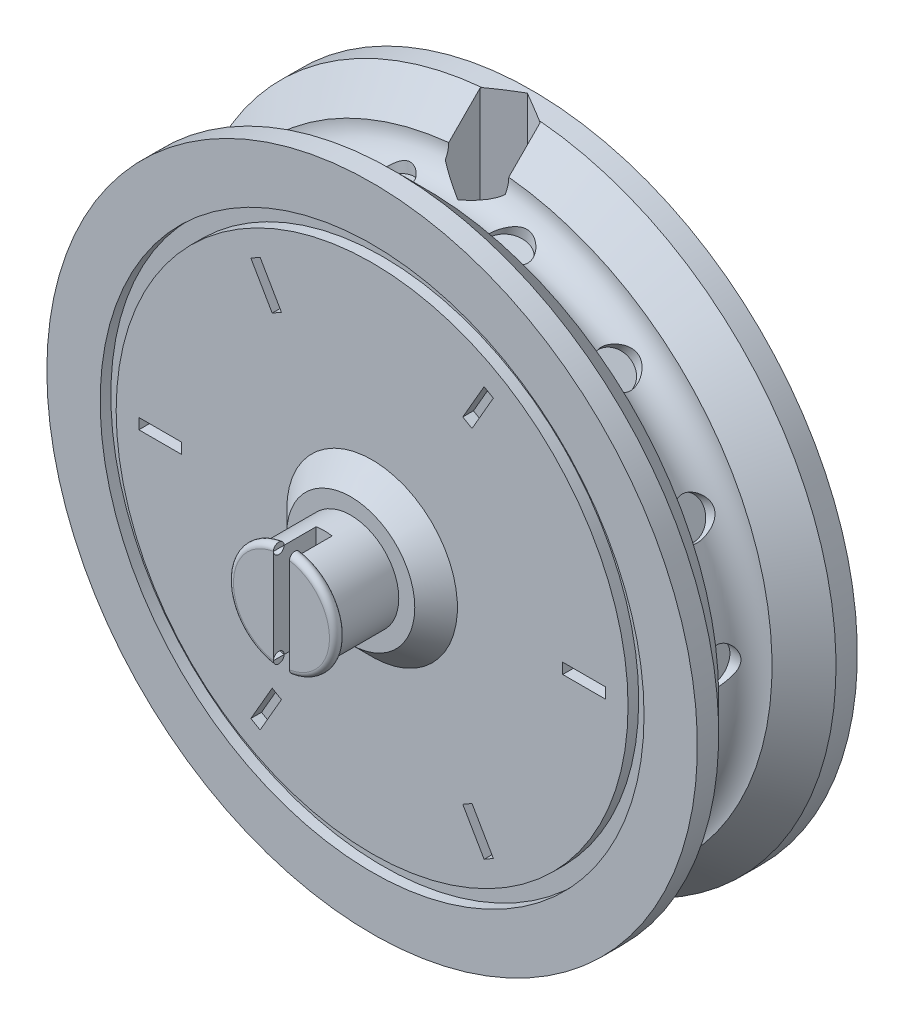
SolidWorks part; units mm, degrees
ref_plane "Alzado" through (0, 0, 0) normal (0, 0, 1) x (1, 0, 0)
ref_plane "Planta" through (0, 0, 0) normal (0, 1, 0) x (1, 0, 0)
ref_plane "Vista lateral" through (0, 0, 0) normal (1, 0, 0) x (0, 0, -1)
ref_plane "Plano1" through (0, 0, -7.7) normal (0, 0, 1) x (1, 0, 0)
sketch "Croquis2" plane through (0, 0, -7.7) normal (0, 0, 1) x (1, 0, 0)
  line L0 (2.829, 4.9) -> (-2.829, 4.9) construction
  line L1 (-3.06, -5.3) -> (3.06, -5.3)
  line L2 (3.06, -5.3) -> (6.1199, 0)
  line L3 (6.1199, 0) -> (3.06, 5.3)
  line L4 (3.06, 5.3) -> (-3.06, 5.3)
  line L5 (-3.06, 5.3) -> (-6.1199, 0)
  line L6 (-6.1199, 0) -> (-3.06, -5.3)
  line L8 (-8.4293, 0) -> (-4.2147, -7.3)
  line L9 (-4.2147, -7.3) -> (4.2147, -7.3)
  line L10 (4.2147, -7.3) -> (8.4293, 0)
  line L11 (8.4293, 0) -> (4.2147, 7.3)
  line L12 (4.2147, 7.3) -> (-4.2147, 7.3)
  line L13 (-4.2147, 7.3) -> (-8.4293, 0)
  circle A0 centre (0, 0) radius 5.3 construction
  circle A1 centre (0, 0) radius 7.3 construction
  dimension "D1" = 0.4
  dimension "D2" = 2
extrude "Saliente-Extruir1" add sketch "Croquis2" along normal up to surface (7.7 mm away)
sketch "Croquis3" plane through (0, -7.3, 0) normal (0, -1, 0) x (1, 0, 0)
  circle A0 centre (0, -4) radius 1.65
  circle A1 centre (0, -4) radius 1.65 construction
extrude "Cortar-Extruir1" cut sketch "Croquis3" against normal through all both and the other way through all
sketch "Croquis4" plane through (0, 0, 0) normal (0, 1, 0) x (1, 0, 0)
  line L0 (0, 7.7) -> (0, -7.3)
  line L1 (-4.2147, 7.7) -> (4.2147, 7.7) construction
  line L2 (0, -7.3) -> (30.5, -7.3)
  line L3 (30.5, -7.3) -> (30.5, -5.3)
  line L4 (30.5, -5.3) -> (27.5, -2.3)
  line L5 (27.5, -2.3) -> (27.5, 2.7) construction
  line L6 (27.5, 2.7) -> (30.5, 5.7)
  line L7 (30.5, 5.7) -> (30.5, 7.7)
  line L8 (30.5, 7.7) -> (0, 7.7)
  line L9 (25, 0.2) -> (0, 0.2) construction
  line L10 (15.25, -7.3) -> (15.25, 0.2) construction
  line L11 (15.25, 0.2) -> (15.25, 7.7) construction
  arc A1 (27.5, 2.7) -> (27.5, -2.3) centre (27.5, 0.2) ccw
  dimension "D1" = 5
  dimension "D2" = 25
  dimension "D3" = 15
  dimension "D4" = 3
  dimension "D5" = 2
revolve "Revolución1" add sketch "Croquis4" angle 360 about L0
sketch "Croquis5" plane through (0, 4.9, 0) normal (0, 1, 0) x (1, 0, 0)
  circle A0 centre (0, 4) radius 2.6
  circle A1 centre (0, 4) radius 1.65 construction
  dimension "D1" = 5.2
  dimension "D2" = 0
extrude "Cortar-Extruir2" cut sketch "Croquis5" against normal through all
sketch "Croquis6" plane through (0, 0, 0) normal (0, 1, 0) x (1, 0, 0)
  line L1 (0, 0.75) -> (2.8146, 2.375)
  line L2 (2.8146, 2.375) -> (2.8146, 5.625)
  line L3 (2.8146, 5.625) -> (0, 7.25)
  line L4 (0, 7.25) -> (-2.8146, 5.625)
  line L5 (-2.8146, 5.625) -> (-2.8146, 2.375)
  line L6 (-2.8146, 2.375) -> (0, 0.75)
  circle A0 centre (0, 4) radius 3.25 construction
  dimension "D1" = 6.5
extrude "Cortar-Extruir3" cut sketch "Croquis6" along normal through all
sketch "Croquis7" plane through (0, 0, 7.3) normal (0, 0, 1) x (1, 0, 0)
  circle A0 centre (0, 0) radius 6
  dimension "D1" = 12
extrude "Saliente-Extruir2" add sketch "Croquis7" along normal blind 2
sketch "Croquis8" plane through (0, 0, 9.3) normal (0, 0, 1) x (1, 0, 0)
  circle A0 centre (0, 0) radius 4.5
  dimension "D1" = 9
extrude "Saliente-Extruir3" add sketch "Croquis8" along normal blind 5.5
chamfer "Chaflán1" distance 2 angle 45 1 edges at (6, 0, 7.3)
sketch "Croquis9" plane through (0, 0, 0) normal (0, 1, 0) x (1, 0, 0)
  line L0 (-4.5, -14.8) -> (-4.5, -15.3) construction
  line L1 (0, -14.8) -> (0, -15.8)
  line L2 (-4.5, -14.8) -> (4.5, -14.8) construction
  line L3 (0, -15.8) -> (-4.5, -15.8)
  line L4 (-4.5, -15.8) -> (-4.5, -14.8)
  line L5 (-4.5, -14.8) -> (0, -14.8)
  circle A0 centre (-4.5, -15.3) radius 0.5
  dimension "D1" = 1
revolve "Revolución2" add sketch "Croquis9" angle 360 about L1 region at (-2.0552, 0, 15.3) region at (-4.7122, 0, 15.3)
sketch "Croquis10" plane through (0, 0, 15.8) normal (0, 0, 1) x (1, 0, 0)
  line L1 (-0.75, 5) -> (0.75, 5)
  line L2 (-0.75, 5) -> (-0.75, -5)
  line L3 (-0.75, -5) -> (0.75, -5)
  line L4 (0.75, 5) -> (0.75, -5)
  line L5 (-0.75, 5) -> (0.75, -5) construction
  line L6 (-0.75, -5) -> (0.75, 5) construction
  circle A0 centre (0, 0) radius 5 construction
  point P0 (0, 0)
  dimension "D1" = 1.5
extrude "Cortar-Extruir6" cut sketch "Croquis10" against normal blind 4
sketch "Croquis12" plane through (0, 0, -7.7) normal (0, 0, -1) x (-1, 0, 0)
  line L1 (6.1199, 0) -> (3.06, 5.3)
  line L2 (3.06, 5.3) -> (-3.06, 5.3)
  line L3 (-3.06, 5.3) -> (-6.1199, 0)
  line L4 (-6.1199, 0) -> (-3.06, -5.3)
  line L5 (-3.06, -5.3) -> (3.06, -5.3)
  line L6 (3.06, -5.3) -> (6.1199, 0)
  circle A0 centre (0, 0) radius 5.3 construction
extrude "Cortar-Extruir7" cut sketch "Croquis12" against normal blind 8
sketch "Croquis13" plane through (0, 0, 0) normal (1, 0, 0) x (0, 0, -1)
  line L0 (0.2, 25) -> (0.2, -25) construction
  line L1 (0.2, 25) -> (-2.3, 25) construction
  line L2 (-2.3, 25) -> (0.2, 25) construction
  line L3 (0.2, 25) -> (2.7, 25) construction
  line L4 (2.7, 27.3556) -> (2.7, -27.4077) construction
  line L5 (-2.3, 27.5) -> (-2.3, -27.5) construction
  arc A0 (-2.3, 27.5) -> (0.75, 25.0613) centre (0.2, 27.5) ccw construction
  arc A1 (1.4, -25.3069) -> (-2.3, -27.5) centre (0.2, -27.5) ccw construction
sketch "Croquis14" plane through (0, 0, 7.3) normal (0, 0, 1) x (1, 0, 0)
  line L0 (0, 25) -> (0, -25) construction
  line L1 (0, 25) -> (0, -25) construction
  line L3 (25, 25) -> (-25, 25)
  line L4 (25, 25) -> (25, -25)
  line L5 (25, -25) -> (-25, -25)
  line L6 (-25, 25) -> (-25, -25)
  line L7 (25, 25) -> (-25, -25) construction
  line L8 (25, -25) -> (-25, 25) construction
  circle A0 centre (0, 0) radius 25
sketch "Croquis15" plane through (0, 0, 7.3) normal (0, 0, 1) x (1, 0, 0)
  circle A0 centre (0, 0) radius 24
  circle A1 centre (0, 0) radius 25.5
  circle A2 centre (0, 0) radius 30.5 construction
  dimension "D1" = 5
  dimension "D2" = 1.5
extrude "Cortar-Extruir8" cut sketch "Croquis15" against normal blind 1
ref_plane "Plano2" through (30.5, 0, 0) normal (1, 0, 0) x (0, 0, -1)
sketch "Croquis16" plane through (30.5, 0, 0) normal (1, 0, 0) x (0, 0, -1)
  circle A0 centre (0, 0) radius 1.75
  dimension "D1" = 3.5
extrude "Cortar-Extruir10" cut sketch "Croquis16" against normal blind 6
pattern_circular "MatrizC1" count 14 over 360 about axis through (0, 0, -7.7) along (0, 0, -1) of "Cortar-Extruir10"
sketch "Croquis17" plane through (0, 0, 7.3) normal (0, 0, 1) x (1, 0, 0)
  line L0 (19.8705, 0) -> (0, 0) construction
  line L1 (21.8705, 0.5) -> (17.8705, 0.5)
  line L2 (21.8705, 0.5) -> (21.8705, -0.5)
  line L3 (21.8705, -0.5) -> (17.8705, -0.5)
  line L4 (17.8705, 0.5) -> (17.8705, -0.5)
  line L5 (21.8705, 0.5) -> (17.8705, -0.5) construction
  line L6 (21.8705, -0.5) -> (17.8705, 0.5) construction
  point P0 (19.8705, 0)
  dimension "D2" = 4
  dimension "D1" = 1
extrude "Cortar-Extruir11" cut sketch "Croquis17" against normal blind 1
pattern_circular "MatrizC2" count 6 over 360 about axis through (0, 0, 7.3) along (0, 0, -1) of "Cortar-Extruir11"
